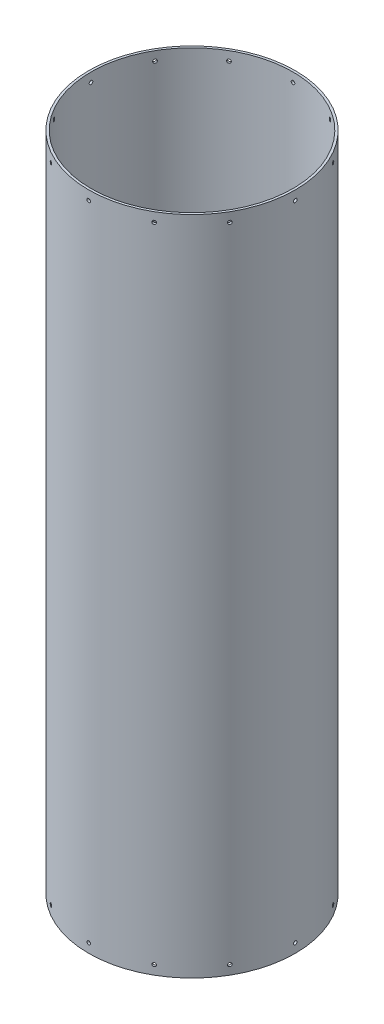
SolidWorks part; units mm, degrees
material "Hexcel AS4C (3000 Filaments)"
ref_plane "Front Plane" through (0, 0, 0) normal (0, 0, 1) x (1, 0, 0)
ref_plane "Top Plane" through (0, 0, 0) normal (0, 1, 0) x (1, 0, 0)
ref_plane "Right Plane" through (0, 0, 0) normal (1, 0, 0) x (0, 0, -1)
sketch "Sketch1" plane through (0, 0, 0) normal (0, 1, 0) x (1, 0, 0)
  circle A0 centre (0, 0) radius 139.7
  circle A1 centre (0, 0) radius 142.875
  dimension "D1" = 279.4
  dimension "D2" = 3.175
extrude "Boss-Extrude1" add sketch "Sketch1" along normal blind 914.4
ref_plane "Plane1" through (142.875, 0, 0) normal (1, 0, 0) x (0, 0, -1)
hole_wizard "#10 (0.1935) Diameter Hole1" positions "Sketch2" profile "Sketch3" hole size "#10" standard "ANSI Inch" end condition up to next
sketch "Sketch2" plane through (142.875, 0, 0) normal (1, 0, 0) x (0, 0, -1)
  line L0 (0, 157.1625) -> (0, -157.1625) construction
  line L1 (142.875, 914.4) -> (-142.875, 914.4) construction
  point P0 (0, 901.7)
  dimension "D1" = 12.7
sketch "Sketch3" plane through (142.875, 901.7, 0) normal (0, 1, 0) x (0, 0, -1)
  line L0 (0, 0) -> (0, 333.7101)
  line L1 (0, 333.7101) -> (2.4574, 333.7101)
  line L2 (2.4574, 333.7101) -> (2.4574, 0)
  line L5 (2.4574, 0) -> (0, 0)
  line L11 (0, -6.35) -> (0, 107.95) construction
  dimension "Thru Hole Dia." = 4.9149
  dimension "Thru Hole Depth" = 333.7101
pattern_circular "CirPattern1" count 12 over 360 about axis through (0, 914.4, 0) along (0, 1, 0) of "#10 (0.1935) Diameter Hole1"
ref_plane "Plane2" through (0, 457.2, 0) normal (0, 1, 0) x (1, 0, 0)
mirror "Mirror1" about plane through (0, 457.2, 0) normal (0, 1, 0) of "CirPattern1"
